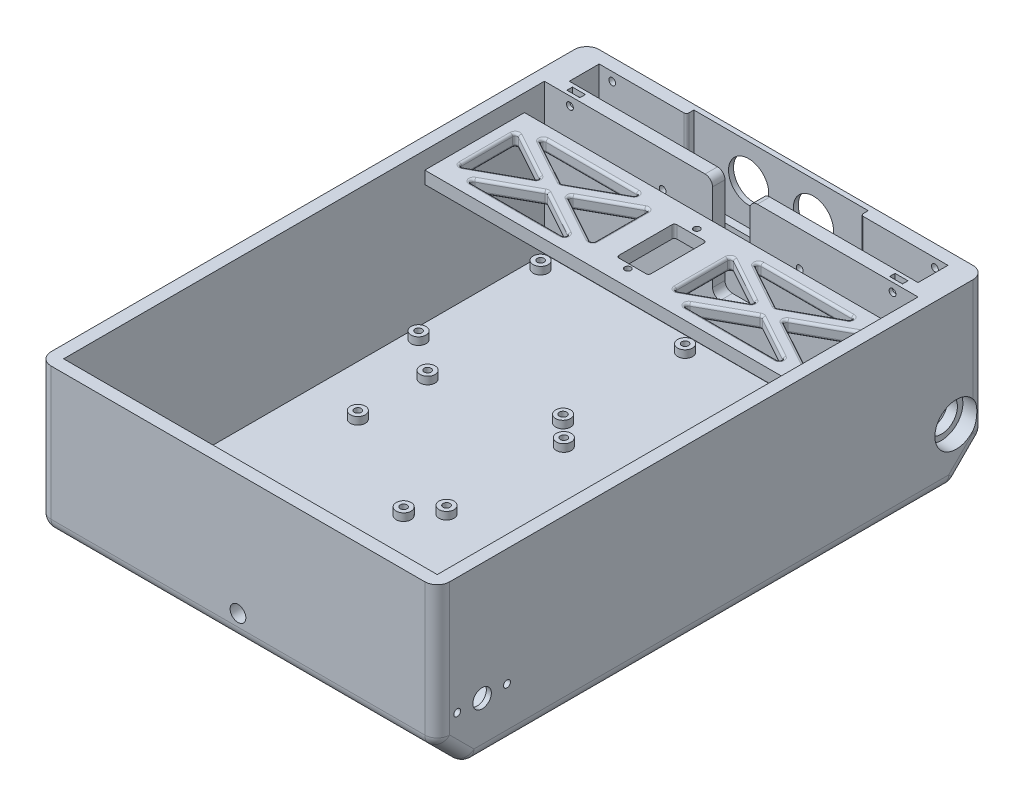
SolidWorks part; units mm, degrees
ref_plane "Front Plane" through (0, 0, 0) normal (0, 0, 1) x (1, 0, 0)
ref_plane "Top Plane" through (0, 0, 0) normal (0, 1, 0) x (1, 0, 0)
ref_plane "Right Plane" through (0, 0, 0) normal (1, 0, 0) x (0, 0, -1)
sketch "Main Body" plane through (0, 0, 0) normal (0, 1, 0) x (1, 0, 0)
  line L0 (-75, 110) -> (75, 110)
  line L1 (-75, -105) -> (75, -105)
  line L2 (-75, -105) -> (-75, 105)
  line L3 (-75, 105) -> (75, 105)
  line L4 (75, -105) -> (75, 105)
  line L5 (-75, -105) -> (75, 105) construction
  line L6 (-75, 105) -> (75, -105) construction
  line L7 (80, -105) -> (80, 105)
  line L8 (-75, -110) -> (75, -110)
  line L9 (-80, -105) -> (-80, 105)
  line L10 (-80, -110) -> (80, -110) construction
  line L11 (-80, -110) -> (-80, 110) construction
  line L12 (80, -110) -> (80, 110) construction
  line L13 (-80, 110) -> (80, 110) construction
  arc A0 (-75, -110) -> (-80, -105) centre (-75, -105) cw
  arc A1 (80, -105) -> (75, -110) centre (75, -105) cw
  arc A2 (75, 110) -> (80, 105) centre (75, 105) cw
  arc A3 (-75, 110) -> (-80, 105) centre (-75, 105) ccw
  point P0 (0, 0)
  dimension "D4" = 5
  dimension "D1" = 75
  dimension "D2" = 210
  dimension "D3" = 5
extrude "Boss-Extrude1" add sketch "Main Body" along normal blind 8 contours L1 L4 L3 L2 | L9 L8 L7 L0 L4 L1 L2 L3 region at (0, 0, -107.2797) region at (0, 0, 0)
extrude "Boss-Extrude3" add sketch "Main Body<4>" along normal blind 60 from surface starting at face at (0, 8, 0)
sketch "Main Body<4>" plane through (0, 0, 0) normal (0, 1, 0) x (1, 0, 0) same geometry as "Main Body"
sketch "Sketch1" plane through (75, 0, 0) normal (-1, 0, 0) x (0, 0, 1)
  line L0 (105, 68) -> (105, 8) construction
  line L1 (-105, 8) -> (105, 8) construction
  line L2 (79, 15.5) -> (105, 15.5)
  line L3 (79, 8) -> (105, 8)
  line L4 (79, 8) -> (79, 34)
  line L5 (79, 34) -> (105, 34)
  line L6 (105, 8) -> (105, 34)
  line L7 (79, 8) -> (105, 34) construction
  line L8 (79, 34) -> (105, 8) construction
  circle A0 centre (92, 21) radius 13
  line M2 (-105, 8) -> (105, 8)
  line M3 (105, 8) -> (105, 68)
  dimension "D1" = 26
  dimension "D2" = 7.5
extrude "Boss-Extrude4" add sketch "Sketch1" along normal up to surface (150 mm away) contours A0 L4 M2 | A0 L3 M3 region at (75, 10.5201, 82.0674) region at (75, 10.5201, 101.9326) up to face at (-75, 38, 0)
sketch "Sketch2" plane through (0, 0, 0) normal (1, 0, 0) x (0, 0, -1)
  line L0 (-105, 68) -> (-105, 15.5) construction
  line L1 (-105, 8) -> (-79, 8)
  line L2 (-105, 8) -> (-105, 15.5)
  line L3 (-105, 15.5) -> (-79, 15.5)
  line L4 (-79, 8) -> (-79, 15.5)
  line L5 (105, 8) -> (-79, 8) construction
  line L6 (-79, 8) -> (-79, 15.5) construction
  line L7 (-79, 15.5) -> (-80.2208, 15.5) construction
extrude "Cut-Extrude1" cut sketch "Sketch2" against normal mid plane 12
sketch "Sketch3" plane through (0, 8, 0) normal (0, 1, 0) x (1, 0, 0)
  line L0 (75, -105) -> (-75, -105) construction
  line L1 (-4, -79) -> (-11, -79)
  line L2 (-4, -79) -> (-4, -105)
  line L3 (-4, -105) -> (-11, -105)
  line L4 (-11, -79) -> (-11, -105)
  line L5 (0, 0) -> (0, -105) construction
  line L6 (-75, -79) -> (-6, -79) construction
  line L7 (11, -79) -> (11, -105)
  line L8 (4, -105) -> (11, -105)
  line L9 (4, -79) -> (4, -105)
  line L10 (4, -79) -> (11, -79)
  line L11 (-6, -103.7792) -> (-6, -92) construction
  dimension "D1" = 5
  dimension "D2" = 4
extrude "Boss-Extrude5" add sketch "Sketch3" along normal blind 20
sketch "Sketch4" plane through (0, 8, 0) normal (0, 1, 0) x (1, 0, 0)
  line L0 (-75, -105) -> (-75, 105) construction
  line L1 (-75, 93) -> (75, 93)
  line L2 (-75, 93) -> (-75, 88)
  line L3 (-75, 88) -> (75, 88)
  line L4 (75, 93) -> (75, 88)
  line L5 (75, 105) -> (75, -105) construction
  line L6 (-75, 105) -> (75, 105) construction
  dimension "D1" = 17
  dimension "D2" = 5
extrude "Boss-Extrude6" add sketch "Sketch4" along normal up to surface (60 mm away) up to face at (0, 68, 0)
sketch "Sketch5" plane through (80, 0, 0) normal (1, 0, 0) x (0, 0, -1)
  circle A0 centre (-92, 21) radius 3.5 construction
  circle A1 centre (-92, 21) radius 3.5
  circle A2 centre (-92, 21) radius 3.7
  dimension "D1" = 0.2
extrude "Cut-Extrude4" cut sketch "Sketch5" against normal up to next contours A1 | A2 A1 region at (80, 21, 92) region at (80, 21, 95.5953)
sketch "Sketch6" plane through (-75, 0, 0) normal (1, 0, 0) x (0, 0, -1)
  circle A0 centre (-92, 21) radius 13
  dimension "D1" = 26
extrude "Cut-Extrude5" cut sketch "Sketch6" against normal offset from surface (3 mm away) 2 up to face at (-80, 34, 0)
mirror "Mirror1" about plane through (0, 0, 0) normal (1, 0, 0) of "Cut-Extrude4"
sketch "Sketch8" plane through (75, 0, 0) normal (-1, 0, 0) x (0, 0, 1)
  circle A0 centre (92, 21) radius 13
  dimension "D1" = 26
extrude "Cut-Extrude6" cut sketch "Sketch8" against normal offset from surface (3 mm away) 2 up to face at (80, 21, 88.3)
sketch "Sketch10" plane through (80, 0, 0) normal (1, 0, 0) x (0, 0, -1)
  circle A1 centre (-82, 21) radius 1.25
  circle A2 centre (-82, 21) radius 1.25
  circle A3 centre (-102, 21) radius 1.25
  circle A4 centre (-102, 21) radius 1.25
  circle A5 centre (-92, 21) radius 12.5
  circle A6 centre (-92, 21) radius 12.5
  circle A63 centre (-102, 21) radius 1.375
  circle A64 centre (-82, 21) radius 1.375
  dimension "D4" = 2.75
extrude "Cut-Extrude7" cut sketch "Sketch10" against normal up to next contours A2 | A64 A2 | A4 | A63 A4 region at (80, 21, 82) region at (80, 21, 102) region at (80, 21, 103.3361) region at (80, 21, 83.3361)
mirror "Mirror3" about plane through (0, 0, 0) normal (1, 0, 0) of "Cut-Extrude7"
sketch "Sketch11" plane through (80, 0, 0) normal (1, 0, 0) x (0, 0, -1)
  circle A0 centre (98.375, 21.05) radius 4.425 construction
  circle A1 centre (98.375, 21.05) radius 4.425
  circle A3 centre (98.375, 21.05) radius 6.425
  dimension "D1" = 2
extrude "Cut-Extrude10" cut sketch "Sketch11" against normal blind 5 contours A1 | A3 A1 region at (80, 21.05, -98.375) region at (80, 21.05, -92.1317)
sketch "Sketch12" plane through (-75, 0, 0) normal (1, 0, 0) x (0, 0, -1)
  line L0 (93, 8) -> (105, 8) construction
  line L1 (93, 68) -> (105, 68)
  line L2 (93, 68) -> (93, 8)
  line L3 (93, 8) -> (105, 8)
  line L4 (105, 68) -> (105, 8)
  line L6 (93, 68) -> (93, 8) construction
  line L7 (93, 68) -> (105, 68) construction
  circle A2 centre (98.375, 21.05) radius 6.425 construction
  circle A3 centre (98.375, 21.05) radius 6.425
extrude "Boss-Extrude7" add sketch "Sketch12" along normal blind 5 contours A3 L2 L3 L4 L1 region at (-75, 41.5496, -99.082)
sketch "Sketch13" plane through (-80, 0, 0) normal (-1, 0, 0) x (0, 0, 1)
  circle A0 centre (-98.375, 21.05) radius 8.625
  circle A2 centre (-98.375, 21.05) radius 6.425 construction
  dimension "D1" = 17.25
extrude "Cut-Extrude11" cut sketch "Sketch13" against normal blind 6
mirror "Mirror4" about plane through (0, 0, 0) normal (1, 0, 0) of "Boss-Extrude7", "Cut-Extrude11"
sketch "Sketch14" plane through (0, 8, 0) normal (0, 1, 0) x (1, 0, 0)
  line L0 (-4, -105) -> (-4, -79) construction
  line L1 (-4, -95) -> (4, -95)
  line L2 (-4, -95) -> (-4, -105)
  line L3 (-4, -105) -> (4, -105)
  line L4 (4, -95) -> (4, -105)
  dimension "D1" = 10
extrude "Boss-Extrude9" add sketch "Sketch14" along normal blind 5
sketch "Sketch15" plane through (0, 0, 110) normal (0, 0, 1) x (1, 0, 0)
  arc A4 (3.15, 19.5) -> (-3.15, 19.5) centre (0, 19.5) ccw
  arc A5 (-3.15, 19.5) -> (3.15, 19.5) centre (0, 19.5) ccw
  arc A6 (3, 19.5) -> (-3, 19.5) centre (0, 19.5) ccw construction
  dimension "D1" = 3.15
extrude "Cut-Extrude12" cut sketch "Sketch15" against normal up to next contours A4 A5 region at (0, 19.5, 110)
sketch "Sketch16" plane through (0, 0, 0) normal (0, -1, 0) x (1, 0, 0)
  circle A0 centre (-12.5, -82) radius 1.475 construction
  circle A1 centre (-70.5, -82) radius 1.475 construction
  circle A2 centre (-70.5, -33) radius 1.475 construction
  circle A3 centre (-12.5, -33) radius 1.475 construction
  circle A4 centre (-4.2, -25) radius 1.475 construction
  circle A5 centre (-55, -21.12) radius 1.475 construction
  circle A6 centre (-55, 6.88) radius 1.475 construction
  circle A7 centre (-4.2, 22.08) radius 1.475 construction
  circle A8 centre (-12.3, 31.18) radius 1.475 construction
  circle A9 centre (24.2, 31.18) radius 1.475 construction
  circle A10 centre (37.8459, 24.117) radius 1.475 construction
  circle A11 centre (59.5541, 24.117) radius 1.475 construction
  circle A12 centre (59.5541, 68.243) radius 1.475 construction
  circle A13 centre (37.8459, 68.243) radius 1.475 construction
  circle A14 centre (24.2, 67.68) radius 1.475 construction
  circle A15 centre (-12.3, 67.68) radius 1.475 construction
  circle A16 centre (-12.5, -82) radius 1.475
  circle A17 centre (-70.5, -82) radius 1.475
  circle A18 centre (-70.5, -33) radius 1.475
  circle A19 centre (-12.5, -33) radius 1.475
  circle A20 centre (-4.2, -25) radius 1.475
  circle A21 centre (-55, -21.12) radius 1.475
  circle A22 centre (-55, 6.88) radius 1.475
  circle A23 centre (-4.2, 22.08) radius 1.475
  circle A24 centre (-12.3, 31.18) radius 1.475
  circle A25 centre (24.2, 31.18) radius 1.475
  circle A26 centre (37.8459, 24.117) radius 1.475
  circle A27 centre (59.5541, 24.117) radius 1.475
  circle A28 centre (59.5541, 68.243) radius 1.475
  circle A29 centre (37.8459, 68.243) radius 1.475
  circle A30 centre (24.2, 67.68) radius 1.475
  circle A31 centre (-12.3, 67.68) radius 1.475
  circle A32 centre (-70.5, -82) radius 1.375
  circle A33 centre (-12.5, -82) radius 1.375
  circle A34 centre (-12.5, -33) radius 1.375
  circle A35 centre (-4.2, -25) radius 1.375
  circle A36 centre (-55, -21.12) radius 1.375
  circle A37 centre (-70.5, -33) radius 1.375
  circle A38 centre (-55, 6.88) radius 1.375
  circle A39 centre (-12.3, 31.18) radius 1.375
  circle A40 centre (-4.2, 22.08) radius 1.375
  circle A41 centre (24.2, 31.18) radius 1.375
  circle A42 centre (37.8459, 24.117) radius 1.375
  circle A43 centre (59.5541, 24.117) radius 1.375
  circle A44 centre (37.8459, 68.243) radius 1.375
  circle A45 centre (59.5541, 68.243) radius 1.375
  circle A46 centre (24.2, 67.68) radius 1.375
  circle A47 centre (-12.3, 67.68) radius 1.375
  dimension "D1" = 2.75
extrude "Cut-Extrude13" cut sketch "Sketch16" against normal up to next contours A47 | A46 | A44 | A45 | A35 | A37 | A36 | A38 | A39 | A40 | A41 | A42 | A43 | A32 | A33 | A19 region at (-70.5, 0, -82) region at (-12.5, 0, -82) region at (-4.2, 0, -25) region at (-55, 0, -21.12) region at (-70.5, 0, -33) region at (-55, 0, 6.88) region at (-12.3, 0, 31.18) region at (-4.2, 0, 22.08) region at (24.2, 0, 31.18) region at (37.8459, 0, 24.117) region at (59.5541, 0, 24.117) region at (37.8459, 0, 68.243) region at (59.5541, 0, 68.243) region at (24.2, 0, 67.68) region at (-12.3, 0, 67.68)
sketch "Sketch18" plane through (75, 0, 0) normal (-1, 0, 0) x (0, 0, 1)
  line L1 (-80, 61.1) -> (-40, 61.1)
  line L2 (-80, 61.1) -> (-80, 56.1)
  line L3 (-80, 56.1) -> (-40, 56.1)
  line L4 (-40, 61.1) -> (-40, 56.1)
  line L5 (-88, 68) -> (105, 68) construction
  dimension "D1" = 5
  dimension "D2" = 30
  dimension "D3" = 40
  dimension "D4" = 6.9
extrude "Boss-Extrude11" add sketch "Sketch18" along normal up to next
sketch "Sketch19" plane through (0, 68, 0) normal (0, 1, 0) x (1, 0, 0)
  line L1 (-6.425, 71.625) -> (6.425, 71.625)
  line L2 (-6.425, 71.625) -> (-6.425, 48.375)
  line L3 (-6.425, 48.375) -> (6.425, 48.375)
  line L4 (6.425, 71.625) -> (6.425, 48.375)
  line L12 (-75, 80) -> (-75, 40)
  line L13 (-75, 40) -> (75, 40)
  line L14 (75, 40) -> (75, 80)
  line L15 (75, 80) -> (-75, 80)
  line L16 (-75, 80) -> (-75, 40)
  line L17 (-75, 40) -> (75, 40)
  line L18 (75, 40) -> (75, 80)
  line L19 (75, 80) -> (-75, 80)
  point P4 (0, 71.625)
  point P8 (0, 80)
  point P12 (6.425, 60)
  point P13 (75, 60)
  dimension "D1" = 23.25
  dimension "D2" = 12.85
  dimension "D3" = 0
extrude "Cut-Extrude14" cut sketch "Sketch19" against normal up to next contours L4 L1 L2 L3 region at (0, 68, -60)
sketch "Sketch21" plane through (0, 0, -110) normal (0, 0, -1) x (-1, 0, 0)
  circle A1 centre (-64.75, 64.5) radius 1.3
  circle A2 centre (-64.75, 64.5) radius 1.3
  circle A3 centre (64.75, 64.5) radius 1.3
  circle A4 centre (64.75, 64.5) radius 1.3
  circle A44 centre (-64.75, 64.5) radius 1.375
  circle A45 centre (64.75, 64.5) radius 1.375
  dimension "D3" = 2.75
extrude "Cut-Extrude16" cut sketch "Sketch21" against normal up to surface (22 mm away) contours A44 A2 | A2 | A45 A4 | A4 region at (64.75, 64.5, -110) region at (-64.75, 64.5, -110) region at (66.0861, 64.5, -110) region at (-63.4139, 64.5, -110) up to face at (0, 38, -88)
ref_plane "Plane1" through (0, 0, -90.5) normal (0, 0, -1) x (-1, 0, 0)
sketch "Sketch22" plane through (0, 0, -90.5) normal (0, 0, -1) x (-1, 0, 0)
  line L0 (-67.35, 66.0011) -> (-67.35, 68)
  line L1 (-62.15, 66.0011) -> (-64.75, 67.5022)
  line L2 (-64.75, 67.5022) -> (-67.35, 66.0011)
  line L3 (-67.35, 66.0011) -> (-67.35, 62.9989)
  line L4 (-67.35, 62.9989) -> (-64.75, 61.4978)
  line L5 (-64.75, 61.4978) -> (-62.15, 62.9989)
  line L6 (-62.15, 62.9989) -> (-62.15, 66.0011)
  line L7 (-67.35, 68) -> (-62.15, 68)
  line L8 (-62.15, 68) -> (-62.15, 66.0011)
  line L9 (-70, 68) -> (70, 68) construction
  line L10 (0, 0) -> (0, 68) construction
  line L11 (75, 68) -> (-75, 68) construction
  line L12 (64.75, 61.4978) -> (62.15, 62.9989)
  line L13 (67.35, 62.9989) -> (64.75, 61.4978)
  line L14 (64.75, 67.5022) -> (67.35, 66.0011)
  line L15 (67.35, 66.0011) -> (67.35, 62.9989)
  line L16 (67.35, 66.0011) -> (67.35, 68)
  line L17 (62.15, 62.9989) -> (62.15, 66.0011)
  line L18 (62.15, 68) -> (62.15, 66.0011)
  line L19 (67.35, 68) -> (62.15, 68)
  line L20 (62.15, 66.0011) -> (64.75, 67.5022)
  circle A0 centre (-64.75, 64.5) radius 2.6 construction
  circle A1 centre (-64.75, 64.5) radius 1.375 construction
  dimension "D1" = 5.2
extrude "Cut-Extrude17" cut sketch "Sketch22" against normal mid plane 2.2 contours L20 L17 L12 L13 L15 L14 | L18 L20 L14 L16 L19 | L5 L6 L1 L2 L3 L4 | L8 L7 L0 L2 L1 region at (67.2943, 67.0006, -90.5) region at (64.75, 64.5, -90.5) region at (-64.75, 64.5, -90.5) region at (-62.2057, 67.0006, -90.5)
sketch "Sketch23" plane through (0, 0, -110) normal (0, 0, -1) x (-1, 0, 0)
  circle A0 centre (64.75, 64.5) radius 2.5
  circle A1 centre (-64.75, 64.5) radius 2.5
  circle A2 centre (64.75, 64.5) radius 1.375 construction
  circle A3 centre (-64.75, 64.5) radius 1.375 construction
  dimension "D1" = 5
  dimension "D2" = 5
extrude "Cut-Extrude18" cut sketch "Sketch23" against normal mid plane 2.5
sketch "Sketch24" plane through (0, 61.1, 0) normal (0, 1, 0) x (1, 0, 0)
  circle A0 centre (0, 46.475) radius 1.2502
  arc A1 (0.4, 45.5583) -> (-0.4, 45.5583) centre (0, 46.475) ccw construction
  circle A2 centre (0, 74.175) radius 1.2502
  arc A3 (-0.4, 75.0917) -> (0, 73.1748) centre (0, 74.175) ccw construction
  point P5 (0.4, 45.5583)
  dimension "D1" = 0.25
extrude "Cut-Extrude19" cut sketch "Sketch24" against normal up to next
sketch "Sketch25" plane through (0, 61.1, 0) normal (0, 1, 0) x (1, 0, 0)
  line L1 (-11.3, 80) -> (11.3, 80)
  line L2 (-11.3, 80) -> (-11.3, 40)
  line L3 (-11.3, 40) -> (11.3, 40)
  line L4 (-75, 80) -> (-75, 40)
  line L5 (-75, 40) -> (75, 40)
  line L6 (75, 40) -> (75, 80)
  line L7 (75, 80) -> (-75, 80)
  line L8 (-75, 80) -> (-75, 40)
  line L9 (-75, 40) -> (75, 40)
  line L10 (75, 40) -> (75, 80)
  line L11 (75, 80) -> (-75, 80)
  line L12 (11.3, 80) -> (11.3, 40)
  line L13 (-11.3, 80) -> (11.3, 40) construction
  line L14 (-11.3, 40) -> (11.3, 80) construction
  line L15 (0, 80) -> (0, 40) construction
  line L16 (70, 75) -> (70, 45)
  line L17 (-70, 75) -> (-16.3, 75)
  line L18 (-70, 75) -> (-70, 45)
  line L19 (-70, 45) -> (-16.3, 45)
  line L20 (-16.3, 75) -> (-16.3, 45)
  line L21 (-70, 75) -> (-16.3, 45) construction
  line L22 (-70, 45) -> (-16.3, 75) construction
  line L23 (70, 75) -> (16.3, 45) construction
  line L24 (70, 45) -> (16.3, 75) construction
  line L25 (70, 75) -> (16.3, 75)
  line L26 (16.3, 75) -> (16.3, 45)
  line L27 (70, 45) -> (16.3, 45)
  line L28 (-75, 60) -> (-11.3, 60) construction
  line L29 (75, 60) -> (11.3, 60) construction
  line L30 (-70, 71.9362) -> (-48.3314, 60)
  line L31 (-16.3, 71.9362) -> (-37.9686, 60)
  line L32 (70, 71.9362) -> (48.3314, 60)
  line L33 (-48.3314, 60) -> (-70, 48.0638)
  line L34 (48.3314, 60) -> (70, 48.0638)
  line L35 (-65.199, 45) -> (-43.15, 57.1458)
  line L36 (65.199, 45) -> (43.15, 57.1458)
  line L37 (-43.15, 57.1458) -> (-21.101, 45)
  line L38 (43.15, 57.1458) -> (21.101, 45)
  line L39 (16.3, 71.9362) -> (37.9686, 60)
  line L40 (-37.9686, 60) -> (-16.3, 48.0638)
  line L41 (37.9686, 60) -> (16.3, 48.0638)
  line L42 (-65.199, 75) -> (-43.15, 62.8542)
  line L43 (65.199, 75) -> (43.15, 62.8542)
  line L44 (-43.15, 62.8542) -> (-21.101, 75)
  line L45 (43.15, 62.8542) -> (21.101, 75)
  line L46 (-75, 40) -> (-75, 80) construction
  line L47 (-75, 40) -> (75, 40) construction
  point P2 (0, 60)
  point P9 (-43.15, 60)
  point P10 (75, 60)
  point P24 (43.15, 60)
  point P62 (-54.1745, 68.9271)
  dimension "D2" = 150
  dimension "D3" = 5
  dimension "D4" = 5
  dimension "D5" = 5
  dimension "D6" = 26.6686
  dimension "D7" = 140.199
  dimension "D1" = 0
extrude "Cut-Extrude21" cut sketch "Sketch25" against normal up to next contours L37 L35 L19 | L33 L30 L18 | L42 L44 L17 | L31 L40 L20 | L41 L39 L26 | L45 L43 L25 | L36 L38 L27 | L32 L34 L16 region at (62.7771, 61.1, -60) region at (43.15, 61.1, -70.9514) region at (43.15, 61.1, -49.0486) region at (23.5229, 61.1, -60) region at (-43.15, 61.1, -70.9514) region at (-62.7771, 61.1, -60) region at (-23.5229, 61.1, -60) region at (-43.15, 61.1, -49.0486)
sketch "Sketch26" plane through (-80, 0, 0) normal (-1, 0, 0) x (0, 0, 1)
  line L0 (-110, 12.649) -> (-97.351, 0)
  line L1 (-110, 68) -> (-110, 0) construction
  line L2 (105, 0) -> (-105, 0) construction
  line L3 (-97.351, 0) -> (-92.351, 0)
  line L4 (-92.351, 0) -> (-110, 17.649)
  line L5 (-110, 17.649) -> (-110, 12.649)
  line L6 (-110, 12.649) -> (-110, 0)
  line L7 (-110, 0) -> (-97.351, 0)
  circle A1 centre (-98.375, 21.05) radius 8.625 construction
  line M5 (-105, 15.5273) -> (-105, 0)
  line M6 (-105, 0) -> (105, 0)
  dimension "D1" = 2
  dimension "D2" = 5
  dimension "D3" = 45
extrude "Cut-Extrude22" cut sketch "Sketch26" against normal up to next contours L6 L7 L0 M5 | L0 M5 M6 region at (-80, 5.1771, -107.7053) region at (-80, 2.5497, -102.4503)
mirror "Mirror5" about plane through (0, 0, 0) normal (0, 0, 1) of "Cut-Extrude22"
fillet "Fillet1" radius 5 14 edges at (80, 3.8245, -101.1755) (78.5355, 11.1845, -108.5355) (-80, 3.8245, -101.1755) (-78.5355, 11.1845, -108.5355) (80, 3.8245, 101.1755) (78.5355, 11.1845, 108.5355) (-80, 3.8245, 101.1755) (-78.5355, 11.1845, 108.5355) (0, 0, -97.351) (0, 12.649, -110) (0, 0, 97.351) (0, 12.649, 110) (-80, 0, 0) (80, 0, 0)
fillet "Fillet2" radius 1 76 edges at (-32.1255, 56.1, -51.0729) (-32.1255, 61.1, -51.0729) (-21.101, 58.6, -45) (-43.15, 61.1, -45) (-43.15, 56.1, -45) (-54.1745, 56.1, -51.0729) (-65.199, 58.6, -45) (-54.1745, 61.1, -51.0729) (-43.15, 58.6, -57.1458) (32.1255, 56.1, -68.9271) (32.1255, 61.1, -68.9271) (21.101, 58.6, -75) (43.15, 61.1, -75) (43.15, 56.1, -75) (54.1745, 56.1, -68.9271) (65.199, 58.6, -75) (54.1745, 61.1, -68.9271) (43.15, 58.6, -62.8542) (54.1745, 61.1, -51.0729) (54.1745, 56.1, -51.0729) (43.15, 56.1, -45) (65.199, 58.6, -45) (43.15, 61.1, -45) (21.101, 58.6, -45) (32.1255, 61.1, -51.0729) (43.15, 58.6, -57.1458) (32.1255, 56.1, -51.0729) (59.1657, 61.1, -65.9681) (59.1657, 56.1, -65.9681) (70, 56.1, -60) (70, 58.6, -71.9362) (70, 61.1, -60) (70, 58.6, -48.0638) (59.1657, 61.1, -54.0319) (48.3314, 58.6, -60) (59.1657, 56.1, -54.0319) (-54.1745, 61.1, -68.9271) (-54.1745, 56.1, -68.9271) (-43.15, 56.1, -75) (-65.199, 58.6, -75) (-43.15, 61.1, -75) (-21.101, 58.6, -75) (-32.1255, 61.1, -68.9271) (-43.15, 58.6, -62.8542) (-32.1255, 56.1, -68.9271) (-59.1657, 56.1, -54.0319) (-59.1657, 61.1, -54.0319) (-70, 58.6, -48.0638) (-70, 61.1, -60) (-70, 56.1, -60) (-59.1657, 56.1, -65.9681) (-70, 58.6, -71.9362) (-59.1657, 61.1, -65.9681) (-48.3314, 58.6, -60) (-27.1343, 61.1, -65.9681) (-27.1343, 56.1, -65.9681) (-16.3, 56.1, -60) (-16.3, 58.6, -71.9362) (-16.3, 61.1, -60) (-16.3, 58.6, -48.0638) (-27.1343, 61.1, -54.0319) (-37.9686, 58.6, -60) (-27.1343, 56.1, -54.0319) (27.1343, 56.1, -54.0319) (27.1343, 61.1, -54.0319) (16.3, 58.6, -48.0638) (16.3, 61.1, -60) (16.3, 56.1, -60) (27.1343, 56.1, -65.9681) (16.3, 58.6, -71.9362) (27.1343, 61.1, -65.9681) (37.9686, 58.6, -60) (6.425, 58.6, -48.375) (-6.425, 58.6, -48.375) (-6.425, 58.6, -71.625) (6.425, 58.6, -71.625)
sketch "Sketch33" plane through (0, 0, -110) normal (0, 0, -1) x (-1, 0, 0)
  circle A0 centre (-13, 53.9999) radius 8.075
  circle A1 centre (13, 53.9999) radius 8.075
  circle A2 centre (-13, 53.9999) radius 7.3 construction
  circle A3 centre (13, 53.9999) radius 7.3 construction
  dimension "D1" = 16.15
extrude "Cut-Extrude27" cut sketch "Sketch33" against normal up to next
sketch "Sketch34" plane through (0, 0, -93) normal (0, 0, -1) x (-1, 0, 0)
  circle A0 centre (27.525, 54) radius 1.35 construction
  circle A1 centre (27.525, 54) radius 1.35
  circle A2 centre (-27.525, 54) radius 1.35 construction
  circle A3 centre (-27.525, 54) radius 1.35
  circle A4 centre (-27.525, 54) radius 1.375
  circle A5 centre (27.525, 54) radius 1.375
  dimension "D1" = 2.75
  dimension "D2" = 2.75
extrude "Cut-Extrude28" cut sketch "Sketch34" against normal up to next contours A3 | A1 region at (-27.525, 54, -93) region at (27.525, 54, -93)
sketch "Sketch35" plane through (0, 68, 0) normal (0, 1, 0) x (1, 0, 0)
  line L0 (70, 93) -> (-70, 93) construction
  line L1 (-7.5, 93) -> (7.5, 93)
  line L2 (-7.5, 93) -> (-7.5, 88)
  line L3 (-7.5, 88) -> (7.5, 88)
  line L4 (7.5, 93) -> (7.5, 88)
  line L5 (-7.5, 93) -> (7.5, 88) construction
  line L6 (-7.5, 88) -> (7.5, 93) construction
  line L7 (-75, 88) -> (75, 88) construction
  point P0 (0, 90.5)
  dimension "D1" = 15
extrude "Cut-Extrude29" cut sketch "Sketch35" against normal offset from surface (41 mm away) 19 up to face at (-4.2, 8, -23.625)
fillet "Fillet4" radius 3 9 edges at (0, 8, 95) (-7.5, 28, 79) (-7.5, 28, 105) (7.5, 28, 105) (7.5, 28, 79) (-7.5, 68, -90.5) (7.5, 68, -90.5) (-7.5, 27, -90.5) (7.5, 27, -90.5)
fillet "Fillet5" radius 1 1 edges at (0, 13, 95)
sketch "Sketch36" plane through (0, 68, 0) normal (0, 1, 0) x (1, 0, 0)
  line L0 (-70, 105) -> (70, 105) construction
  line L1 (-35, 108) -> (35, 108)
  line L2 (-35, 108) -> (-35, 105)
  line L3 (-35, 105) -> (35, 105)
  line L4 (35, 108) -> (35, 105)
  line L5 (-75, 110) -> (75, 110) construction
  point P6 (0, 108)
  dimension "D1" = 70
  dimension "D2" = 2
extrude "Cut-Extrude30" cut sketch "Sketch36" against normal blind 30
fillet "Fillet6" radius 1 2 edges at (35, 53, -105) (-35, 53, -105)
sketch "Sketch37" plane through (0, 8, 0) normal (0, 1, 0) x (1, 0, 0)
  line L8 (-4, -79) -> (-4, -92)
  line L9 (-4, -92) -> (4, -92)
  line L10 (4, -92) -> (4, -79)
  line L11 (4, -79) -> (75, -79)
  line L12 (75, -79) -> (75, 88)
  line L13 (75, 88) -> (-75, 88)
  line L14 (-75, 88) -> (-75, -79)
  line L15 (-75, -79) -> (-4, -79)
  line L16 (-4, -79) -> (-4, -92)
  line L17 (-4, -92) -> (4, -92)
  line L18 (4, -92) -> (4, -79)
  line L19 (4, -79) -> (75, -79)
  line L20 (75, -79) -> (75, 88)
  line L21 (75, 88) -> (-75, 88)
  line L22 (-75, 88) -> (-75, -79)
  line L23 (-75, -79) -> (-4, -79)
  circle A0 centre (-12.5, 82) radius 1.375 construction
  circle A1 centre (-4.2, 25) radius 1.375 construction
  circle A2 centre (-12.5, 33) radius 1.475 construction
  circle A3 centre (-70.5, 33) radius 1.375 construction
  circle A4 centre (-55, 21.12) radius 1.375 construction
  circle A5 centre (-55, -6.88) radius 1.375 construction
  circle A6 centre (-12.3, -31.18) radius 1.375 construction
  circle A7 centre (-4.2, -22.08) radius 1.375 construction
  circle A8 centre (24.2, -31.18) radius 1.375 construction
  circle A9 centre (37.8459, -24.117) radius 1.375 construction
  circle A10 centre (59.5541, -24.117) radius 1.375 construction
  circle A11 centre (59.5541, -68.243) radius 1.375 construction
  circle A12 centre (37.8459, -68.243) radius 1.375 construction
  circle A13 centre (24.2, -67.68) radius 1.375 construction
  circle A14 centre (-12.3, -67.68) radius 1.375 construction
  circle A15 centre (-70.5, 82) radius 1.375 construction
  circle A16 centre (-12.5, 82) radius 1.375
  circle A17 centre (-4.2, 25) radius 1.375
  circle A18 centre (-12.5, 33) radius 1.475
  circle A19 centre (-70.5, 33) radius 1.375
  circle A20 centre (-55, 21.12) radius 1.375
  circle A21 centre (-55, -6.88) radius 1.375
  circle A22 centre (-12.3, -31.18) radius 1.375
  circle A23 centre (-4.2, -22.08) radius 1.375
  circle A24 centre (24.2, -31.18) radius 1.375
  circle A25 centre (37.8459, -24.117) radius 1.375
  circle A26 centre (59.5541, -24.117) radius 1.375
  circle A27 centre (59.5541, -68.243) radius 1.375
  circle A28 centre (37.8459, -68.243) radius 1.375
  circle A29 centre (24.2, -67.68) radius 1.375
  circle A30 centre (-12.3, -67.68) radius 1.375
  circle A31 centre (-70.5, 82) radius 1.375
  circle A32 centre (-12.3, -67.68) radius 3
  circle A33 centre (24.2, -67.68) radius 3
  circle A34 centre (37.8459, -68.243) radius 3
  circle A35 centre (59.5541, -68.243) radius 3
  circle A36 centre (24.2, -31.18) radius 3
  circle A37 centre (37.8459, -24.117) radius 3
  circle A38 centre (59.5541, -24.117) radius 3
  circle A39 centre (-4.2, -22.08) radius 3
  circle A40 centre (-12.3, -31.18) radius 3
  circle A41 centre (-4.2, 25) radius 3
  circle A42 centre (-55, -6.88) radius 3
  circle A43 centre (-55, 21.12) radius 3
  circle A44 centre (-12.5, 33) radius 3
  circle A45 centre (-12.5, 82) radius 3
  circle A46 centre (-70.5, 82) radius 3
  circle A47 centre (-70.5, 33) radius 3
  circle M9 centre (-4.2, 25) radius 1.375
  circle M10 centre (59.5541, -68.243) radius 1.375
  circle M11 centre (37.8459, -68.243) radius 1.375
  circle M12 centre (24.2, -67.68) radius 1.375
  circle M13 centre (-70.5, 33) radius 1.375
  circle M14 centre (-55, 21.12) radius 1.375
  circle M15 centre (-55, -6.88) radius 1.375
  circle M16 centre (-12.3, -31.18) radius 1.375
  circle M17 centre (-4.2, -22.08) radius 1.375
  circle M18 centre (24.2, -31.18) radius 1.375
  circle M19 centre (37.8459, -24.117) radius 1.375
  circle M20 centre (59.5541, -24.117) radius 1.375
  circle M21 centre (-70.5, 82) radius 1.375
  circle M22 centre (-12.5, 82) radius 1.375
  circle M23 centre (-12.5, 33) radius 1.475
  circle M24 centre (-12.3, -67.68) radius 1.375
  dimension "D2" = 6
  dimension "D1" = 0
extrude "Boss-Extrude12" add sketch "Sketch37" along normal blind 3 contours A46 M21 | A45 M22 | A44 M23 | A41 M9 | A47 M13 | A43 M14 | A42 M15 | A38 M20 | A35 M10 | A34 M11 | A37 M19 | A36 M18 | A33 M12 | A39 M17 | A40 M16 | A32 M24 region at (-15.2151, 8, 67.68) region at (21.2849, 8, 67.68) region at (34.9307, 8, 68.243) region at (56.639, 8, 68.243) region at (21.2849, 8, 31.18) region at (34.9307, 8, 24.117) region at (56.639, 8, 24.117) region at (-7.1151, 8, 22.08) region at (-15.2151, 8, 31.18) region at (-7.1151, 8, -25) region at (-57.9151, 8, 6.88) region at (-57.9151, 8, -21.12) region at (-15.4151, 8, -33) region at (-15.4151, 8, -82) region at (-73.4151, 8, -82) region at (-73.4151, 8, -33)
equation "\"Screw\"= 2.75"
equation "\"D1@Sketch16\"=\"Screw\""
equation "\"D4@Sketch10\"=\"Screw\""
equation "\"D3@Sketch21\"=\"Screw\""
equation "\"D2@Sketch34\"=\"Screw\""
equation "\"D1@Sketch34\"=\"Screw\""
